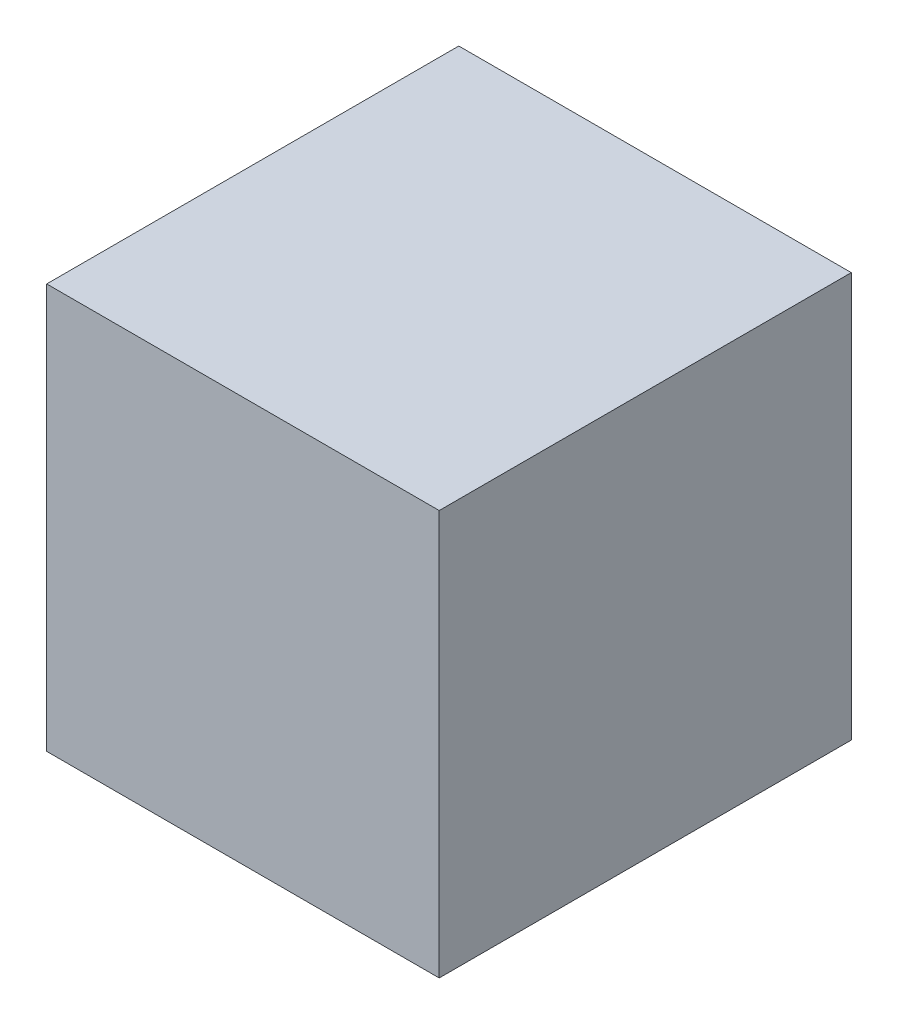
SolidWorks part; units mm, degrees
ref_plane "Front Plane" through (0, 0, 0) normal (0, 0, 1) x (1, 0, 0)
ref_plane "Top Plane" through (0, 0, 0) normal (0, 1, 0) x (1, 0, 0)
ref_plane "Right Plane" through (0, 0, 0) normal (1, 0, 0) x (0, 0, -1)
sketch "Sketch1" plane through (0, 0, 0) normal (0, 0, 1) x (1, 0, 0)
  line L0 (10.0166, 9.6322) -> (10.0166, -29.6653) construction
  line L1 (-9.0331, -29.6653) -> (29.0663, -29.6653)
  line L2 (-9.0331, -29.6653) -> (-9.0331, 9.6322)
  line L3 (-9.0331, 9.6322) -> (29.0663, 9.6322)
  line L4 (29.0663, -29.6653) -> (29.0663, 9.6322)
  line L5 (-9.0331, -10.0166) -> (29.0663, -10.0166) construction
  circle A0 centre (10.0166, -10.0166) radius 3.7971
extrude "Boss-Extrude1" add sketch "Sketch1" along normal blind 40 contours A0 | L1 L4 L3 L2 A0 region at (-8.4858, -10.0166, 0) region at (10.0166, -10.0166, 0)
extrude "Cut-Extrude1" cut sketch "Sketch1<3>" along normal blind 20 contours A0 region at (10.0166, -10.0166, 0)
sketch "Sketch1<3>" plane through (0, 0, 0) normal (0, 0, 1) x (1, 0, 0) same geometry as "Sketch1"
